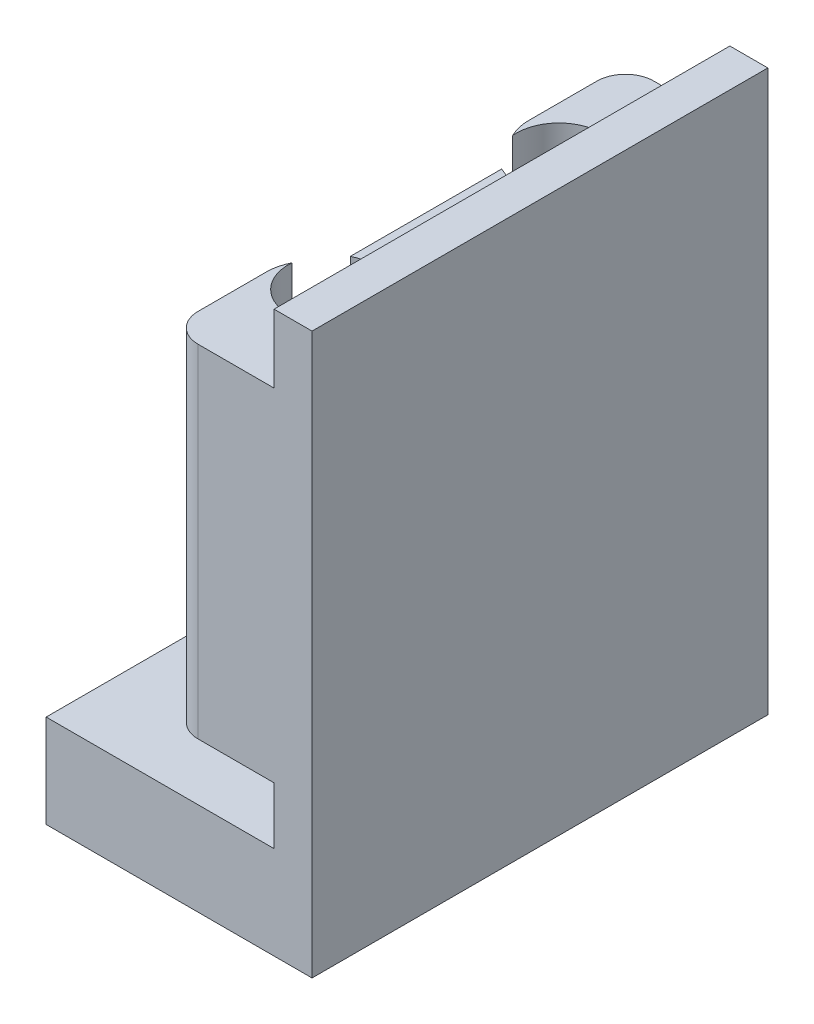
SolidWorks part; units mm, degrees
ref_plane "Front" through (0, 0, 0) normal (0, 0, 1) x (1, 0, 0)
ref_plane "Top" through (0, 0, 0) normal (0, 1, 0) x (1, 0, 0)
ref_plane "Right" through (0, 0, 0) normal (1, 0, 0) x (0, 0, -1)
sketch "Sketch1" plane through (0, 0, 0) normal (0, 1, 0) x (1, 0, 0)
  line L5 (-6, -12) -> (6, -12)
  line L6 (-6, -12) -> (-6, 12)
  line L7 (-6, 12) -> (6, 12)
  line L8 (6, -12) -> (6, 12)
  line L9 (-6, -12) -> (6, 12) construction
  line L10 (-6, 12) -> (6, -12) construction
  point P0 (0, 0)
  dimension "D1" = 12
  dimension "D2" = 24
extrude "Boss-Extrude1" add sketch "Sketch1" along normal blind 4.9
sketch "Sketch2" plane through (0, 0, 0) normal (0, 1, 0) x (1, 0, 0)
  line L0 (6, 12) -> (-6, 12) construction
  line L1 (6, -12) -> (8, -12)
  line L2 (6, -12) -> (6, 12)
  line L3 (6, 12) -> (8, 12)
  line L4 (8, -12) -> (8, 12)
  dimension "D1" = 2
extrude "Boss-Extrude2" add sketch "Sketch2" along normal blind 29.5
sketch "Sketch4" plane through (0, 4.9, 0) normal (0, 1, 0) x (1, 0, 0)
  line L1 (6, -12) -> (0.5, -12)
  line L2 (6, -12) -> (6, 12)
  line L3 (6, 12) -> (0.5, 12)
  line L4 (0.5, -12) -> (0.5, 12)
  line L5 (6, 12) -> (-6, 12) construction
  dimension "D1" = 5.5
extrude "Boss-Extrude4" add sketch "Sketch4" along normal blind 18 from offset 3
sketch "Sketch5" plane through (0.5, 0, 0) normal (-1, 0, 0) x (0, 0, 1)
  line L0 (-12, 25.9) -> (12, 25.9) construction
  line L1 (-4.625, 25.9) -> (4.625, 25.9)
  line L2 (-4.625, 25.9) -> (-4.625, 7.9)
  line L3 (-4.625, 7.9) -> (4.625, 7.9)
  line L4 (4.625, 25.9) -> (4.625, 7.9)
  line L5 (-12, 7.9) -> (12, 7.9) construction
  line L8 (4.625, 25.9) -> (12, 25.9) construction
  line L9 (-4.625, 25.9) -> (-12, 25.9) construction
  dimension "D1" = 9.25
extrude "Cut-Extrude1" cut sketch "Sketch5" against normal blind 1.5
fillet "Fillet1" radius 2.5 2 edges at (0.5, 16.9, 4.625) (0.5, 16.9, -4.625)
sketch "Sketch6" plane through (0, 25.9, 0) normal (0, 1, 0) x (1, 0, 0)
  line L1 (6, -12) -> (6, 12) construction
  line L3 (3, -12) -> (3, -6) construction
  line L4 (0.5, -12) -> (6, -12) construction
  line L5 (3, -6) -> (6, -6) construction
  line L7 (3, 12) -> (3, 6) construction
  line L9 (3, 6) -> (6, 6) construction
  line L10 (6, 12) -> (0.5, 12) construction
  circle A0 centre (3, -6) radius 2.25
  circle A4 centre (3, 6) radius 2.25
  dimension "D3" = 4.5
  dimension "D8" = 4.5
  dimension "D1" = 6
  dimension "D2" = 3
  dimension "D6" = 6
  dimension "D7" = 3
extrude "Cut-Extrude2" cut sketch "Sketch6" against normal through all
fillet "Fillet2" radius 1.5 2 edges at (0.5, 16.9, -12) (0.5, 16.9, 12)
